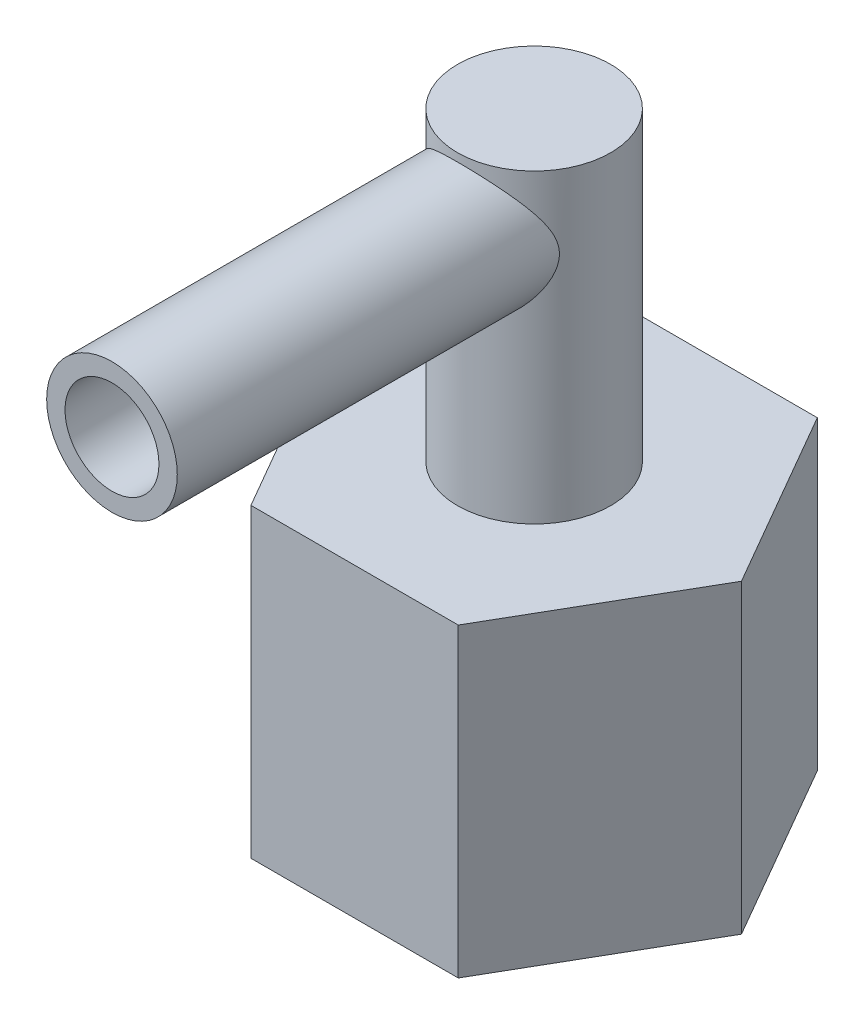
SolidWorks part; units mm, degrees
material "1060 Alloy"
ref_plane "Front Plane" through (0, 0, 0) normal (0, 0, 1) x (1, 0, 0)
ref_plane "Top Plane" through (0, 0, 0) normal (0, 1, 0) x (1, 0, 0)
ref_plane "Right Plane" through (0, 0, 0) normal (1, 0, 0) x (0, 0, -1)
sketch "Sketch1" plane through (0, 0, 0) normal (0, 1, 0) x (1, 0, 0)
  circle A0 centre (0, 0) radius 4.7625
  circle A1 centre (0, 0) radius 3.175
  dimension "D1" = 9.525
extrude "Boss-Extrude1" add sketch "Sketch1" along normal blind 8.3312
sketch "Sketch2" plane through (0, 8.3312, 0) normal (0, 1, 0) x (1, 0, 0)
  line L1 (5.6506, 0) -> (2.8253, 4.8936)
  line L2 (2.8253, 4.8936) -> (-2.8253, 4.8936)
  line L3 (-2.8253, 4.8936) -> (-5.6506, 0)
  line L4 (-5.6506, 0) -> (-2.8253, -4.8936)
  line L5 (-2.8253, -4.8936) -> (2.8253, -4.8936)
  line L6 (2.8253, -4.8936) -> (5.6506, 0)
  circle A0 centre (0, 0) radius 4.8936 construction
extrude "Boss-Extrude2" add sketch "Sketch2" along normal blind 8.3312
sketch "Sketch3" plane through (0, 16.6624, 0) normal (0, 1, 0) x (1, 0, 0)
  circle A0 centre (0, 0) radius 1.5875
  circle A1 centre (0, 0) radius 2.0875
  dimension "D1" = 3.175
  dimension "D2" = 0.5
extrude "Boss-Extrude3" add sketch "Sketch3" along normal blind 8.3312
sketch "Sketch4" plane through (0, 24.9936, 0) normal (0, 1, 0) x (1, 0, 0)
  circle A0 centre (0, 0) radius 2.0875
extrude "Boss-Extrude4" add sketch "Sketch4" along normal blind 0.001
ref_plane "Plane1" through (0, 0, 0) normal (0, 0, 1) x (1, 0, 0)
sketch "Sketch5" plane through (0, 0, 0) normal (0, 0, 1) x (1, 0, 0)
  line L0 (0, 24.9946) -> (0, 22.9946) construction
  line L1 (2.0875, 24.9946) -> (-2.0875, 24.9946) construction
  circle A0 centre (0, 22.9946) radius 1.78
  circle A1 centre (0, 22.9946) radius 1.28
  dimension "D1" = 2
  dimension "D2" = 0.5
extrude "Boss-Extrude5" add sketch "Sketch5" along normal blind 11.5062
sketch "Sketch6" plane through (0, 0, 0) normal (0, -1, 0) x (1, 0, 0)
  circle A0 centre (0, 0) radius 10.2581
extrude "Cut-Extrude1" cut sketch "Sketch6" against normal up to surface (8.3312 mm away) up to face at (0, 8.3312, 0)
